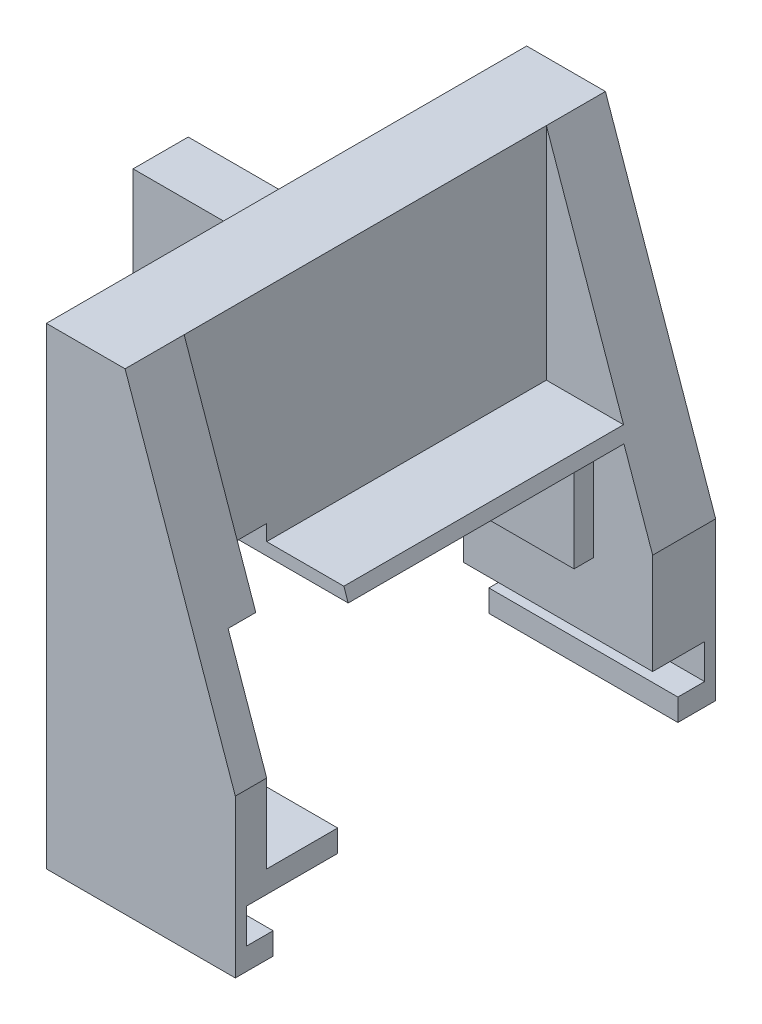
SolidWorks part; units mm, degrees
ref_plane "Front Plane" through (0, 0, 0) normal (0, 0, 1) x (1, 0, 0)
ref_plane "Top Plane" through (0, 0, 0) normal (0, 1, 0) x (1, 0, 0)
ref_plane "Right Plane" through (0, 0, 0) normal (1, 0, 0) x (0, 0, -1)
sketch "Sketch1" plane through (0, 0, 0) normal (0, 0, 1) x (1, 0, 0)
  line L0 (0, 0) -> (0, -30)
  line L1 (0, -30) -> (12, -30)
  line L2 (12, -30) -> (12, -20)
  line L3 (12, -20) -> (5, 0)
  line L4 (5, 0) -> (0, 0)
  dimension "D1" = 30
  dimension "D2" = 12
  dimension "D3" = 10
  dimension "D4" = 5
extrude "Boss-Extrude1" add sketch "Sketch1" against normal blind 30.5
sketch "Sketch4" plane through (0, 0, 0) normal (-1, 0, 0) x (0, 0, 1)
  line L0 (-30.5, 0) -> (-30.5, -30) construction
  line L1 (-26.5, -14.788) -> (-6.5, -14.788)
  line L2 (-26.5, -14.788) -> (-26.5, -30.788)
  line L3 (-26.5, -30.788) -> (-6.5, -30.788)
  line L4 (-6.5, -14.788) -> (-6.5, -30.788)
  point P4 (-26.5, -22.788)
  point P7 (-26.5, -14.788)
  dimension "D1" = 20
  dimension "D2" = 16
  dimension "D3" = 4
extrude "Cut-Extrude2" cut sketch "Sketch4" against normal blind 25 contours L2 L1 L4 L3
ref_plane "Plane1" through (0, 0, -15.25) normal (0, 0, 1) x (1, 0, 0)
sketch "Sketch6" plane through (0, 0, -15.25) normal (0, 0, 1) x (1, 0, 0)
  line L0 (5, 0) -> (5, -14)
  line L1 (5, -14) -> (9.9, -14)
  line L2 (12, -20) -> (5, 0) construction
  line L3 (9.9, -14) -> (5, 0)
  dimension "D1" = 14
extrude "Cut-Extrude4" cut sketch "Sketch6" against normal mid plane 23
ref_plane "Plane2" through (0, -22, 0) normal (0, 1, 0) x (1, 0, 0)
sketch "Sketch7" plane through (0, -22, 0) normal (0, 1, 0) x (1, 0, 0)
  line L0 (8.2588, 28.75) -> (-19.7412, 28.75)
  line L62 (-6.6, 15.25) -> (6.6, 15.25) construction
  line L162 (8.2588, 28.75) -> (8.2588, 25.25)
  line L172 (-19.7412, 25.25) -> (-19.7412, 28.75)
  line L238 (8.2588, 25.25) -> (-19.7412, 25.25)
  point P2 (-7.7994, 28.75)
  point P3 (0, 0)
  point P4 (0, 27.45)
  point P5 (0, 27.45)
  point P8 (0, 0)
  point P9 (0, 27.45)
  point P10 (0, 27.45)
  point P12 (0, 27.45)
  point P13 (0, 28.75)
  point P14 (8.2588, 28.75)
  dimension "D2" = 28
  dimension "D3" = 3.5
  dimension "D7" = 13.5
sketch "Sketch8" plane through (0, 0, 0) normal (-1, 0, 0) x (0, 0, 1)
  line L0 (-8.9912, -13) -> (-1.9912, -13)
  line L2 (-6.5, -30) -> (0, -30) construction
  line L6 (-1.9912, -13) -> (-1.9912, -25)
  line L7 (-1.9912, -25) -> (-8.9912, -25)
  line L9 (-8.9912, -25) -> (-8.9912, -13)
  dimension "D1" = 7
  dimension "D2" = 12
  dimension "D3" = 5
extrude "Cut-Extrude5" cut sketch "Sketch8" against normal through all
sketch "Sketch9" plane through (0, 0, 0) normal (-1, 0, 0) x (0, 0, 1)
  line L0 (-6.5, -26.4) -> (-0.7, -26.4)
  line L1 (-6.5, -25) -> (-6.5, -30) construction
  line L2 (-0.7, -26.4) -> (-0.7, -28.6)
  line L3 (-0.7, -28.6) -> (-2.4, -28.6)
  line L4 (-2.4, -28.6) -> (-2.4, -30.2967)
  line L5 (-2.4, -30.2967) -> (-6.5, -30.2967)
  line L6 (-6.5, -30.2967) -> (-6.5, -26.4)
  line L7 (-6.5, -30) -> (0, -30) construction
  line L8 (-15.25, -6.6) -> (-15.25, 6.6) construction
  line L9 (-24, -30.2967) -> (-24, -26.4)
  line L10 (-28.1, -30.2967) -> (-24, -30.2967)
  line L11 (-28.1, -28.6) -> (-28.1, -30.2967)
  line L12 (-29.8, -28.6) -> (-28.1, -28.6)
  line L13 (-29.8, -26.4) -> (-29.8, -28.6)
  line L14 (-24, -26.4) -> (-29.8, -26.4)
  dimension "D1" = 5.8
  dimension "D2" = 2.2
  dimension "D3" = 1.4
  dimension "D4" = 1.7
extrude "Cut-Extrude6" cut sketch "Sketch9" against normal through all
extrude "Boss-Extrude3" add sketch "Sketch7" along normal blind 8
